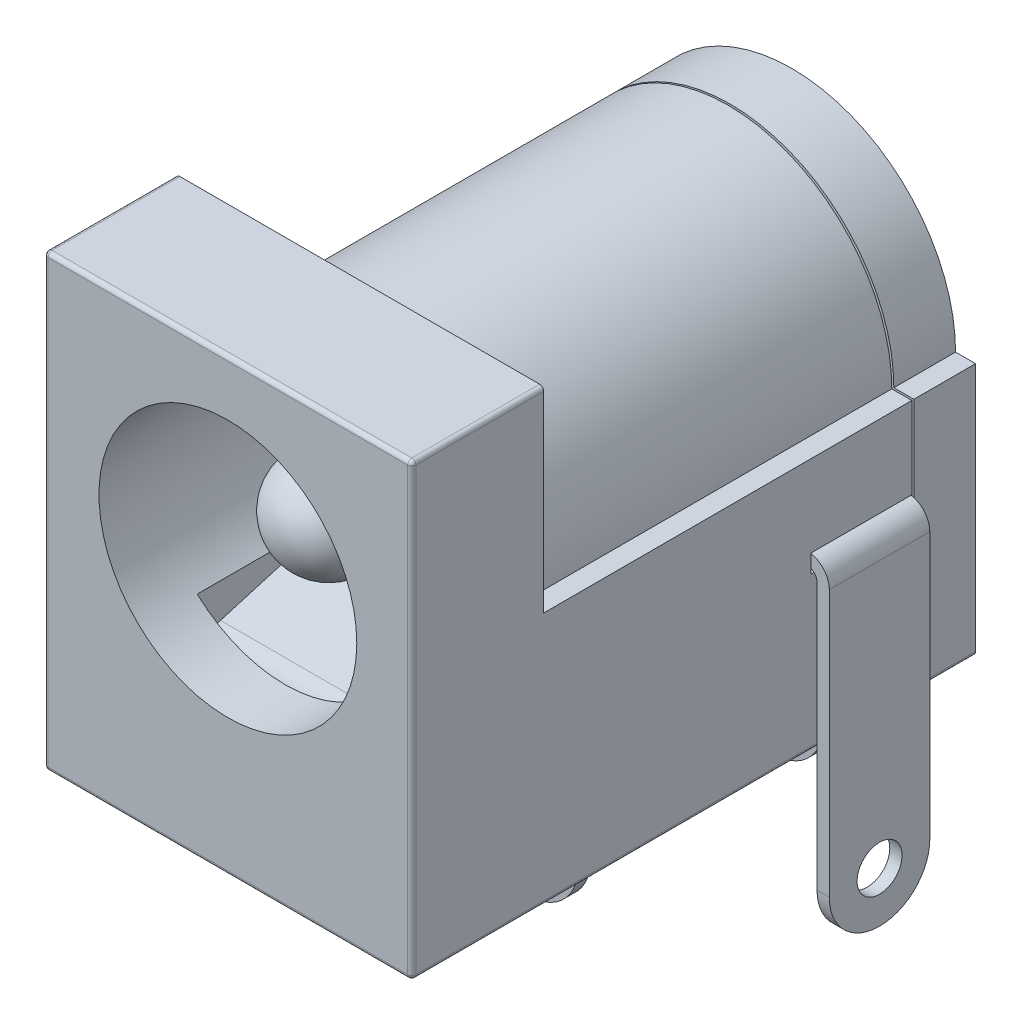
SolidWorks part; units mm, degrees
material "PVC Rígido"
ref_plane "Plano frontal" through (0, 0, 0) normal (0, 0, 1) x (1, 0, 0)
ref_plane "Plano superior" through (0, 0, 0) normal (0, 1, 0) x (1, 0, 0)
ref_plane "Plano direito" through (0, 0, 0) normal (1, 0, 0) x (0, 0, -1)
sketch "Esboço1" plane through (0, 0, 0) normal (0, 0, 1) x (1, 0, 0)
  line L1 (-4.5, 4.5) -> (4.5, 4.5)
  line L2 (-4.5, 4.5) -> (-4.5, -6.5)
  line L3 (-4.5, -6.5) -> (4.5, -6.5)
  line L4 (4.5, 4.5) -> (4.5, -6.5)
  line L5 (-4.5, 4.5) -> (4.5, -6.5) construction
  line L6 (-4.5, -6.5) -> (4.5, 4.5) construction
  circle A0 centre (0, 0) radius 3.155 construction
  point P0 (0, -1)
  dimension "D3" = 6.31
  dimension "D1" = 11
  dimension "D2" = 9
  dimension "D4" = 6.5
extrude "Ressalto-extrusão1" add sketch "Esboço1" along normal mid plane 12.24
sketch "Esboço2" plane through (0, 0, -6.12) normal (0, 0, -1) x (-1, 0, 0)
  line L0 (-4.5, -0.3) -> (-4.01, -0.3)
  line L1 (-4.5, -6.5) -> (-4.5, 4.5) construction
  line L2 (4.5, -6.5) -> (-4.5, -6.5) construction
  line L3 (4.01, -0.3) -> (4.5, -0.3)
  line L4 (4.5, 4.5) -> (4.5, -6.5) construction
  line L9 (-4.5, 4.5) -> (-4.5, -6.5)
  line L10 (-4.5, -6.5) -> (4.5, -6.5)
  line L11 (4.5, -6.5) -> (4.5, 4.5)
  line L12 (4.5, 4.5) -> (-4.5, 4.5)
  line L13 (-4.5, 4.5) -> (-4.5, -0.3)
  line L15 (4.5, -0.3) -> (4.5, 4.5)
  line L16 (4.5, 4.5) -> (-4.5, 4.5)
  arc A0 (-4.01, -0.3) -> (4.01, -0.3) centre (0, -0.3) cw
  point P15 (0, 3.71)
  dimension "D3" = 10.21
  dimension "D1" = 6.2
  dimension "D4" = 8.02
  dimension "D2" = 0
extrude "Corte-extrusão1" cut sketch "Esboço2" against normal offset from surface (9.01 mm away) 3.23 up to face at (0, -1, 6.12)
sketch "Esboço3" plane through (0, 0, -6.12) normal (0, 0, -1) x (-1, 0, 0)
  line L10 (-3.4742, -0.8) -> (-4, -0.8)
  line L11 (-4, -0.8) -> (-4, -6)
  line L12 (-4, -6) -> (4, -6)
  line L13 (4, -6) -> (4, -0.8)
  line L14 (4, -0.8) -> (3.4742, -0.8)
  line L15 (-3.4742, -0.8) -> (-4, -0.8)
  line L16 (-4, -0.8) -> (-4, -6)
  line L17 (-4, -6) -> (4, -6)
  line L18 (4, -6) -> (4, -0.8)
  line L19 (4, -0.8) -> (3.4742, -0.8)
  arc A2 (3.4742, -0.8) -> (-3.4742, -0.8) centre (0, -0.3) ccw
  arc A3 (3.4742, -0.8) -> (-3.4742, -0.8) centre (0, -0.3) ccw
  dimension "D1" = 0.5
extrude "Ressalto-extrusão2" add sketch "Esboço3" along normal blind 0.05
sketch "Esboço4" plane through (0, 0, -6.17) normal (0, 0, -1) x (-1, 0, 0)
  line L5 (-4.01, -0.3) -> (-4.5, -0.3)
  line L6 (-4.5, -0.3) -> (-4.5, -6.5)
  line L7 (-4.5, -6.5) -> (4.5, -6.5)
  line L8 (4.5, -6.5) -> (4.5, -0.3)
  line L9 (4.5, -0.3) -> (4.01, -0.3)
  line L10 (-4.01, -0.3) -> (-4.5, -0.3)
  line L11 (-4.5, -0.3) -> (-4.5, -6.5)
  line L12 (-4.5, -6.5) -> (4.5, -6.5)
  line L13 (4.5, -6.5) -> (4.5, -0.3)
  line L14 (4.5, -0.3) -> (4.01, -0.3)
  arc A1 (4.01, -0.3) -> (-4.01, -0.3) centre (0, -0.3) ccw
  arc A2 (4.01, -0.3) -> (-4.01, -0.3) centre (0, -0.3) ccw
  dimension "D1" = 0
extrude "Ressalto-extrusão3" add sketch "Esboço4" along normal offset from surface (1.51 mm away) 13.8 up to face at (0, -1, 6.12)
sketch "Esboço5" plane through (0, 0, -7.68) normal (0, 0, -1) x (-1, 0, 0)
  line L0 (0.8924, 1.84) -> (-0.8924, 1.84)
  line L1 (4.5, -6.5) -> (-4.5, -6.5) construction
  line L2 (1.28, -6.5) -> (-1.28, -6.5)
  line L3 (1.28, -6.5) -> (1.28, -1.5949)
  line L5 (-1.28, -6.5) -> (-1.28, -1.5949)
  arc A0 (-0.8924, 1.84) -> (-1.28, -1.5949) centre (0, 0) ccw
  arc A1 (1.28, -1.5949) -> (0.8924, 1.84) centre (0, 0) ccw
  dimension "D1" = 4.09
  dimension "D2" = 1.84
  dimension "D3" = 2.56
extrude "Corte-extrusão2" cut sketch "Esboço5" against normal offset from surface (0.45 mm away) 13.35 up to face at (0, -1, 6.12)
sketch "Esboço6" plane through (0, 0, -7.23) normal (0, 0, -1) x (-1, 0, 0)
  line L5 (4.5, -6.5) -> (-4.5, -6.5) construction
  line L8 (1.23, -6.45) -> (1.23, -1.5707)
  line L9 (0.8809, 1.79) -> (-0.8809, 1.79)
  line L10 (-1.23, -1.5707) -> (-1.23, -6.45)
  line L11 (-1.23, -6.45) -> (1.23, -6.45)
  line L12 (1.23, -9.37) -> (1.23, -1.5707)
  line L13 (0.8809, 1.79) -> (-0.8809, 1.79)
  line L14 (-1.23, -1.5707) -> (-1.23, -9.37)
  arc A2 (-1.23, -9.37) -> (1.23, -9.37) centre (0, -9.37) ccw
  arc A4 (1.23, -1.5707) -> (0.8809, 1.79) centre (0, 0) ccw
  arc A5 (-0.8809, 1.79) -> (-1.23, -1.5707) centre (0, 0) ccw
  arc A6 (1.23, -1.5707) -> (0.8809, 1.79) centre (0, 0) ccw
  arc A7 (-0.8809, 1.79) -> (-1.23, -1.5707) centre (0, 0) ccw
  dimension "D2" = 2.46
  dimension "D3" = 4.1
  dimension "D1" = 0.05
extrude "Ressalto-extrusão4" add sketch "Esboço6" along normal blind 0.3
sketch "Esboço8" plane through (0, 0, 6.12) normal (0, 0, 1) x (1, 0, 0)
  circle A0 centre (0, 0) radius 3.155 construction
  circle A1 centre (0, 0) radius 3.155
extrude "Corte-extrusão3" cut sketch "Esboço8" against normal up to surface (12.24 mm away) up to face at (0, -1.6983, -6.12)
sketch "Esboço9" plane through (0, 0, -6.12) normal (0, 0, 1) x (1, 0, 0)
  circle A0 centre (0, 0) radius 1.45
  dimension "D1" = 2.9
extrude "Ressalto-extrusão6" add sketch "Esboço9" along normal offset from surface (0.1 mm away) 0.1 up to face at (3.155, 0, -6.12) offset beyond the face yes
sketch "Esboço10" plane through (0, 0, -6.12) normal (0, 0, 1) x (1, 0, 0)
  circle A0 centre (0, 0) radius 1.25
  dimension "D1" = 2.5
extrude "Ressalto-extrusão7" add sketch "Esboço10" along normal offset from surface (11.02 mm away) 1.22 up to face at (3.155, 0, 6.12)
fillet "Filete1" radius 1.25 1 edges at (1.25, 0, 4.9)
ref_plane "Plano1" through (0, 0, -1.23) normal (0, 0, 1) x (1, 0, 0)
sketch "Esboço11" plane through (0, 0, -1.23) normal (0, 0, 1) x (1, 0, 0)
  line L0 (1.23, -6.5) -> (-1.23, -6.5) construction
  line L3 (1.23, -9.37) -> (1.23, -6.5)
  line L4 (1.23, -6.5) -> (-1.23, -6.5)
  line L5 (-1.23, -6.5) -> (-1.23, -9.37)
  line L6 (1.23, -9.37) -> (1.23, -5.5)
  line L7 (1.23, -5.5) -> (-1.23, -5.5)
  line L8 (-1.23, -5.5) -> (-1.23, -9.37)
  arc A1 (-1.23, -9.37) -> (1.23, -9.37) centre (0, -9.37) ccw
  arc A2 (-1.23, -9.37) -> (1.23, -9.37) centre (0, -9.37) ccw
  dimension "D2" = 1
  dimension "D1" = 0
extrude "Ressalto-extrusão8" add sketch "Esboço11" against normal blind 0.3
sketch "Esboço12" plane through (0, -6.5, 0) normal (0, -1, 0) x (1, 0, 0)
  line L0 (1.23, -1.23) -> (-1.23, -1.23) construction
  line L1 (-1.28, -1.23) -> (-1.23, -1.23)
  line L2 (-1.28, -1.23) -> (-1.28, -6.17)
  line L3 (-1.28, -6.17) -> (1.28, -6.17)
  line L4 (1.28, -1.23) -> (1.28, -6.17)
  line L5 (4.5, -6.17) -> (-4.5, -6.17) construction
  line L6 (-4.5, -6.12) -> (4.5, -6.12) construction
  line L7 (-1.23, -1.53) -> (-1.23, -1.23) construction
  line L8 (1.23, -1.23) -> (1.23, -1.53) construction
  line L9 (1.23, -1.23) -> (1.28, -1.23)
  line L13 (1.23, -1.23) -> (-1.23, -1.23)
  line L14 (-1.23, -1.23) -> (-1.23, -1.53)
  line L15 (-1.23, -1.53) -> (1.23, -1.53)
  line L16 (1.23, -1.53) -> (1.23, -1.23)
  line L18 (-1.23, -1.23) -> (-1.23, -1.53)
  line L19 (-1.23, -1.53) -> (1.23, -1.53)
  line L20 (1.23, -1.53) -> (1.23, -1.23)
  point P12 (-1.23, -1.38)
  point P15 (1.23, -1.38)
  dimension "D1" = 0.05
  dimension "D2" = 0.05
  dimension "D3" = 0.05
  dimension "D4" = 0
extrude "Corte-extrusão4" cut sketch "Esboço12" against normal up to surface (0.5 mm away) up to face at (0, -6, -6.145)
sketch "Esboço13" plane through (0, -6, 0) normal (0, -1, 0) x (1, 0, 0)
  line L0 (4.5, -6.17) -> (-4.5, -6.17) construction
  line L1 (-1.23, -1.53) -> (1.23, -1.53)
  line L2 (-1.23, -1.53) -> (-1.23, -6.17)
  line L3 (-1.23, -6.17) -> (1.23, -6.17)
  line L4 (1.23, -1.53) -> (1.23, -6.17)
extrude "Ressalto-extrusão9" add sketch "Esboço13" along normal up to surface (0.5 mm away) up to face at (0, -6.5, -1.716)
hole_wizard "Furo1" positions "Esboço14" profile "Esboço15" legacy end condition through all
sketch "Esboço14" plane through (0, 0, -7.53) normal (0, 0, -1) x (-1, 0, 0)
  point P0 (0, -9.37)
sketch "Esboço15" plane through (0, -9.37, -7.53) normal (1, 0, 0) x (0, 1, 0)
  line L0 (0, 0) -> (0, 13.65)
  line L1 (0, 13.65) -> (0.55, 13.65)
  line L2 (0.55, 13.65) -> (0.55, 0)
  line L3 (0.55, 0) -> (0, 0)
  line L4 (0, 110) -> (0, -10) construction
  dimension "Diameter" = 1.1
  dimension "Depth" = 13.65
sketch "Esboço16" plane through (0, 0, 0) normal (1, 0, 0) x (0, 0, -1)
  line L1 (-4.72, -3.155) -> (1.53, -3.155) construction
  line L2 (-4.72, -3.155) -> (-4.72, -4.155)
  line L3 (-4.72, -4.155) -> (1.53, -4.155)
  line L4 (1.53, -3.155) -> (1.53, -4.155)
  line L6 (-6.12, -6.5) -> (-6.12, 4.5) construction
  line L7 (1.53, -9.37) -> (1.53, -6.5) construction
  line L8 (-4.72, -3.155) -> (-4.72, -2.155)
  line L9 (-4.72, -2.155) -> (1.53, -2.155)
  line L10 (1.53, -2.155) -> (1.53, -3.155)
  point P4 (-6.12, -3.155)
  dimension "D1" = 1.4
  dimension "D2" = 1
  dimension "D3" = 1
extrude "Corte-extrusão6" cut sketch "Esboço16" against normal mid plane 4.3
sketch "Esboço17" plane through (0, 0, 0) normal (1, 0, 0) x (0, 0, -1)
  line L0 (1.23, -9.37) -> (1.23, -6.5) construction
  line L1 (1.23, -6.5) -> (1.53, -6.5)
  line L2 (1.23, -6.5) -> (1.23, -4.2678)
  line L3 (1.3459, -2.5983) -> (5.02, -2.5983)
  line L4 (1.53, -6.5) -> (1.53, -4.2678)
  line L5 (1.53, -9.37) -> (1.53, -6.5) construction
  line L6 (-6.12, -6.5) -> (6.12, -6.5) construction
  line L7 (-4.2511, -3.05) -> (0.3878, -1.6939)
  line L8 (1.0172, -3.755) -> (-4.1072, -3.755)
  line L9 (6.02, -1.25) -> (-3.65, -1.25)
  line L10 (1.0172, -4.055) -> (-4.1072, -4.055)
  line L11 (-3.5, 1.175) -> (5.795, 1.175)
  line L12 (1.0239, -2.0422) -> (1.1417, -2.4452)
  line L14 (0.8537, -2.5294) -> (0.7359, -2.1264)
  line L15 (0.472, -1.9818) -> (-4.1669, -3.3379)
  line L16 (5.02, -2.5983) -> (5.02, -2.8983)
  line L17 (6.02, -1.25) -> (-3.65, -1.25) construction
  line L18 (-1.545, -4.055) -> (-1.545, -3.755) construction
  line L19 (-4.2511, -3.05) -> (-4.1669, -3.3379) construction
  line L20 (-4.72, -3.155) -> (-4.72, -4.155) construction
  line L21 (5.02, -2.8983) -> (1.3459, -2.8983)
  line L22 (-6.12, 3.155) -> (-6.12, -3.155) construction
  line L23 (-4.72, -4.155) -> (1.53, -4.155) construction
  arc A0 (-4.1072, -4.055) -> (-4.2511, -3.05) centre (-4.1072, -3.5422) cw
  arc A1 (1.0172, -3.755) -> (1.53, -4.2678) centre (1.0172, -4.2678) cw
  arc A2 (0.3878, -1.6939) -> (1.0239, -2.0422) centre (0.5317, -2.1861) cw
  arc A3 (0.7359, -2.1264) -> (0.472, -1.9818) centre (0.5317, -2.1861) ccw
  arc A4 (1.23, -4.2678) -> (1.0172, -4.055) centre (1.0172, -4.2678) ccw
  arc A5 (-4.1669, -3.3379) -> (-4.1072, -3.755) centre (-4.1072, -3.5422) ccw
  arc A6 (1.1417, -2.4452) -> (1.3459, -2.5983) centre (1.3459, -2.3855) ccw
  arc A7 (1.3459, -2.8983) -> (0.8537, -2.5294) centre (1.3459, -2.3855) cw
  point P39 (1.53, -3.755)
  point P42 (0.88, -1.55)
  dimension "D1" = 0.1
  dimension "D5" = 0.925
  dimension "D7" = 0.2128
  dimension "D8" = 0.5128
  dimension "D2" = 0.3
  dimension "D3" = 7
  dimension "D4" = 0.1
  dimension "D6" = 1.8
  dimension "D9" = 0.3
  dimension "D10" = 1
extrude "Ressalto-extrusão10" add sketch "Esboço17" against normal offset from surface 0.1 and the other way offset from surface 0.1 up to face at (-2.15, -3.232, 1.595) other way up to face at (2.15, -3.232, 1.595)
hole_wizard "Furo2" positions "Esboço18" profile "Esboço19" legacy
sketch "Esboço18" plane through (0, 0, -7.53) normal (0, 0, -1) x (-1, 0, 0)
  point P0 (0, 0)
sketch "Esboço19" plane through (0, 0, -7.53) normal (1, 0, 0) x (0, 1, 0)
  line L0 (0, 0) -> (0, 1.3906)
  line L1 (0, 1.3906) -> (0.65, 1)
  line L2 (0.65, 1) -> (0.65, 0)
  line L4 (0.65, 0) -> (0, 0)
  line L6 (0, 1.3906) -> (-0.65, 1) construction
  line L7 (0, -4.2442) -> (0, 117.3081) construction
  dimension "Diameter" = 1.3
  dimension "Depth" = 1
  dimension "Drill Angle" = 118
sketch "Esboço20" plane through (0, 0, 0) normal (1, 0, 0) x (0, 0, -1)
  line L0 (7.53, 0) -> (7.8028, 0) construction
  line L1 (7.53, 0.65) -> (7.8158, 1.145)
  line L2 (7.8158, 1.145) -> (7.5993, 1.27)
  line L3 (7.53, 0.65) -> (7.8028, 0.65) construction
  line L4 (7.5993, 1.27) -> (7.53, 1.15)
  line L5 (7.53, 1.15) -> (7.53, 0.65)
  point P5 (7.53, 0.65)
  dimension "D1" = 2.54
  dimension "D2" = 120
  dimension "D3" = 0.25
revolve "Revolução1" add sketch "Esboço20" angle 360 about L0
sketch "Esboço21" plane through (4.5, 0, 0) normal (1, 0, 0) x (0, 0, -1)
  line L0 (6.17, -0.8) -> (6.17, -6) construction
  line L1 (6.17, -2.3) -> (3.65, -2.3)
  line L2 (6.17, -2.3) -> (6.17, -2.75)
  line L3 (6.17, -2.75) -> (3.65, -2.75)
  line L4 (3.65, -2.3) -> (3.65, -2.75)
  line L6 (6.12, -6.5) -> (6.12, -0.3) construction
  line L7 (-6.12, -6.5) -> (6.12, -6.5) construction
  dimension "D1" = 2.47
  dimension "D2" = 0.45
  dimension "D3" = 4.2
fillet "Filete2" radius 0.3 1 edges at (0.65, 0, -7.53)
fillet "Filete3" radius 0.1 10 edges at (-4.5, -6.5, 0) (-4.5, -6.5, -6.925) (4.5, -6.5, -6.925) (4.5, -6.5, 0) (-4.5, 4.5, 4.505) (4.5, 4.5, 4.505) (4.5, -1, 6.12) (0, 4.5, 6.12) (-4.5, -1, 6.12) (0, -6.5, 6.12)
extrude "Corte-extrusão7" cut sketch "Esboço21" against normal up to surface (0.5 mm away) up to face at (4, -3.4, -6.145)
sketch "Esboço22" plane through (0, 0, -3.65) normal (0, 0, -1) x (-1, 0, 0)
  line L0 (-4.65, -2.85) -> (-4.65, -10.6)
  line L1 (-4.65, -10.6) -> (-4.95, -10.6)
  line L2 (-4.95, -10.6) -> (-4.95, -2.85)
  line L3 (-4.65, -10.6) -> (0, -10.6) construction
  line L4 (-4, -2.3) -> (-4.5, -2.3)
  line L5 (-4.5, -2.3) -> (-4.5, -2.75)
  line L6 (-4.5, -2.75) -> (-4, -2.75)
  line L7 (-4, -2.75) -> (-4, -2.3)
  line L8 (2.05, -2.3) -> (-4.4, -2.3)
  line L10 (-4.4, -2.6) -> (2.05, -2.6)
  line L11 (2.05, -2.6) -> (2.05, -2.3)
  line L12 (4.5, -0.3) -> (4.5, -6.4) construction
  line L13 (2.05, -1.6939) -> (2.05, -3.05) construction
  arc A0 (-4.4, -2.6) -> (-4.65, -2.85) centre (-4.4, -2.85) ccw
  arc A1 (-4.95, -2.85) -> (-4.4, -2.3) centre (-4.4, -2.85) cw
  arc A2 (-1.23, -9.37) -> (1.23, -9.37) centre (0, -9.37) ccw construction
  dimension "D2" = 0.25
  dimension "D4" = 0.55
  dimension "D3" = 0.3
  dimension "D5" = 9.45
  dimension "D1" = 0
extrude "Ressalto-extrusão11" add sketch "Esboço22" along normal blind 2.46
sketch "Esboço23" plane through (4.95, 0, 0) normal (1, 0, 0) x (0, 0, -1)
  line L0 (3.65, -2.85) -> (3.65, -10.6) construction
  line L1 (6.11, -10.6) -> (6.11, -2.85) construction
  line L2 (6.11, -10.6) -> (3.65, -10.6) construction
  line L7 (3.65, -10.6) -> (6.11, -10.6)
  line L8 (6.11, -10.6) -> (6.11, -2.85)
  line L9 (6.11, -2.85) -> (3.65, -2.85)
  line L10 (3.65, -2.85) -> (3.65, -10.6)
  line L11 (3.65, -10.6) -> (6.11, -10.6)
  line L12 (6.11, -10.6) -> (6.11, -9.37)
  line L14 (3.65, -9.37) -> (3.65, -10.6)
  arc A0 (3.65, -9.37) -> (6.11, -9.37) centre (4.88, -9.37) ccw
  line M5 (3.65, -10.6) -> (6.11, -10.6)
  line M6 (6.11, -10.6) -> (6.11, -2.85)
  line M8 (3.65, -2.85) -> (3.65, -10.6)
  dimension "D1" = 0
extrude "Corte-extrusão8" cut sketch "Esboço23" against normal through all contours A0 M8 M5 | A0 L11 M6 region at (4.95, -10.3253, -3.9247) region at (4.95, -10.3253, -5.8353)
hole_wizard "Furo3" positions "Esboço24" profile "Esboço25" legacy end condition through all
sketch "Esboço24" plane through (4.95, 0, 0) normal (1, 0, 0) x (0, 0, -1)
  point P0 (4.88, -9.37)
sketch "Esboço25" plane through (4.95, -9.37, -4.88) normal (0, 1, 0) x (0, 0, -1)
  line L0 (0, 0) -> (0, 9.45)
  line L1 (0, 9.45) -> (0.55, 9.45)
  line L2 (0.55, 9.45) -> (0.55, 0)
  line L3 (0.55, 0) -> (0, 0)
  line L4 (0, 110) -> (0, -10) construction
  dimension "Diameter" = 1.1
  dimension "Depth" = 9.45
equation "\"D1@Filete1\"=\"D1@Esboço10\"/2"
equation "\"D2@Esboço12\"=\"D1@Esboço12\""
equation "\"D3@Esboço12\"=\"D2@Esboço12\""
